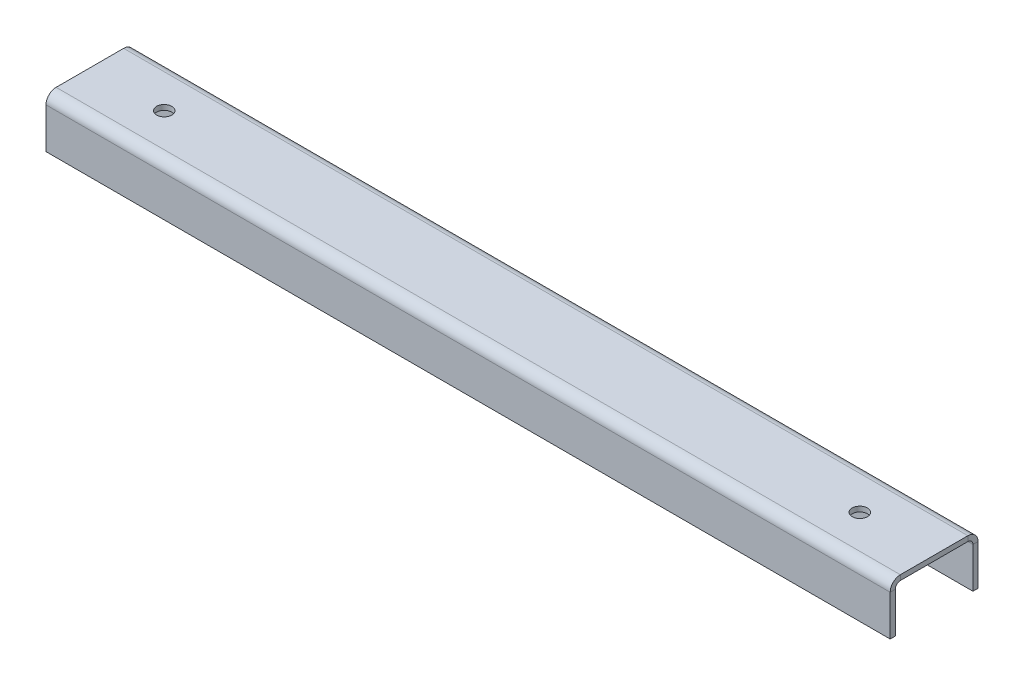
SolidWorks part; units mm, degrees
note: The reader was unsure of these and kept them because the rebuilt part matched: flange length of "Edge-Flange1".
ref_plane "Front Plane" through (0, 0, 0) normal (0, 0, 1) x (1, 0, 0)
ref_plane "Top Plane" through (0, 0, 0) normal (0, 1, 0) x (1, 0, 0)
ref_plane "Right Plane" through (0, 0, 0) normal (1, 0, 0) x (0, 0, -1)
sketch "Sketch1" plane through (448.0804, -33993.0636, -9815.3299) normal (0, 1, 0) x (1, 0, 0)
  line L1 (-249.6317, -1685.0336) -> (250.3683, -1685.0336)
  line L2 (-249.6317, -1685.0336) -> (-249.6317, -1725.0336)
  line L3 (-249.6317, -1725.0336) -> (250.3683, -1725.0336)
  line L4 (250.3683, -1685.0336) -> (250.3683, -1725.0336)
  circle A0 centre (-205.6317, -1705.0336) radius 4.5
  circle A1 centre (206.3683, -1705.0336) radius 4.5
  dimension "D3" = 9
  dimension "D4" = 9
  dimension "D5" = 412
  dimension "D6" = 44
  dimension "D1" = 40
  dimension "D2" = 500
  dimension "D7" = 44
base flange "Base-Flange1" sketch "Sketch1" thickness 3 reverse thickness direction no parameters "D1"=0.7366
edge flange "Edge-Flange1" sketch "Sketch10" flange profiles "Sketch10", "Sketch11" flange angle 90 flange length 30 flange position bend outside bend radius 3 thickness 3 relief rectangular parameters "D6"=10, "D8"=1
sketch "Sketch10" plane through (0, -33996.0636, -8090.2964) normal (0, 0, 1) x (-1, 0, 0)
  line L2 (-698.4487, 0) -> (-698.4487, 27)
  line L3 (-698.4487, 27) -> (-198.4487, 27)
  line L4 (-198.4487, 27) -> (-198.4487, 0)
  line L7 (-198.4487, 0) -> (-698.4487, 0) construction
  line L8 (-198.4487, 0) -> (-698.4487, 0)
sketch "Sketch11" plane through (0, -33996.0636, -8130.2964) normal (0, 0, -1) x (1, 0, 0)
  line L0 (698.4487, 0) -> (198.4487, 0) construction
  line L1 (698.4487, 0) -> (198.4487, 0)
  line L2 (198.4487, 0) -> (198.4487, 27)
  line L3 (198.4487, 27) -> (698.4487, 27)
  line L4 (698.4487, 27) -> (698.4487, 0)
bend "EdgeBend1" bend radius 3 bend angle 90 parameters "D5"=1
bend "EdgeBend2" bend radius 3 bend angle 90 parameters "D5"=2
sketch "Bend-Lines1" [suppressed] plane through (0, 0, 0) normal (0, 1, 0) x (1, 0, 0)
sketch "Bounding-Box1" [suppressed] plane through (0, 0, 0) normal (0, 1, 0) x (1, 0, 0)
sheet metal parameters "Sheet-Metal1" thickness 3 parameters "D1"=0.7366
flat pattern "Flat-Pattern1" [suppressed]
sketch "Bend-Lines2" plane through (0, 0, 0) normal (0, 1, 0) x (1, 0, 0)
sketch3d "Bounding-Box2" [suppressed]
  line L0 (-250.3683, -1725.0336, 0) -> (249.6317, -1725.0336, 0) construction
  line L1 (-250.3683, -1685.0336, 0) -> (249.6317, -1685.0336, 0) construction
  line L2 (-250.3683, -1725.0336, 0) -> (-250.3683, -1685.0336, 0) construction
  line L3 (249.6317, -1725.0336, 0) -> (249.6317, -1685.0336, 0) construction
sheet metal parameters "Sheet-Metal2" thickness 3 parameters "D1"=0.7366
flat pattern "Flat-Pattern1" [suppressed]
sketch "Bend-Lines2" plane through (0, -33993.0636, 0) normal (0, 1, 0) x (1, 0, 0)
  line L0 (698.4487, 8133.595) -> (198.4487, 8133.595) construction
  line L1 (198.4487, 8086.9977) -> (698.4487, 8086.9977) construction
  line L2 (698.4487, 8133.595) -> (198.4487, 8133.595) construction
  line L3 (198.4487, 8086.9977) -> (698.4487, 8086.9977) construction
sketch3d "Bounding-Box2" [suppressed]
  line L0 (698.4487, 8059.699, 0) -> (198.4487, 8059.699, 0) construction
  line L1 (698.4487, 8160.8937, 0) -> (198.4487, 8160.8937, 0) construction
  line L2 (698.4487, 8059.699, 0) -> (698.4487, 8160.8937, 0) construction
  line L3 (198.4487, 8059.699, 0) -> (198.4487, 8160.8937, 0) construction
bend of the flat pattern "Flatten-<EdgeBend1>1"
bend of the flat pattern "Flatten-<EdgeBend2>1"
